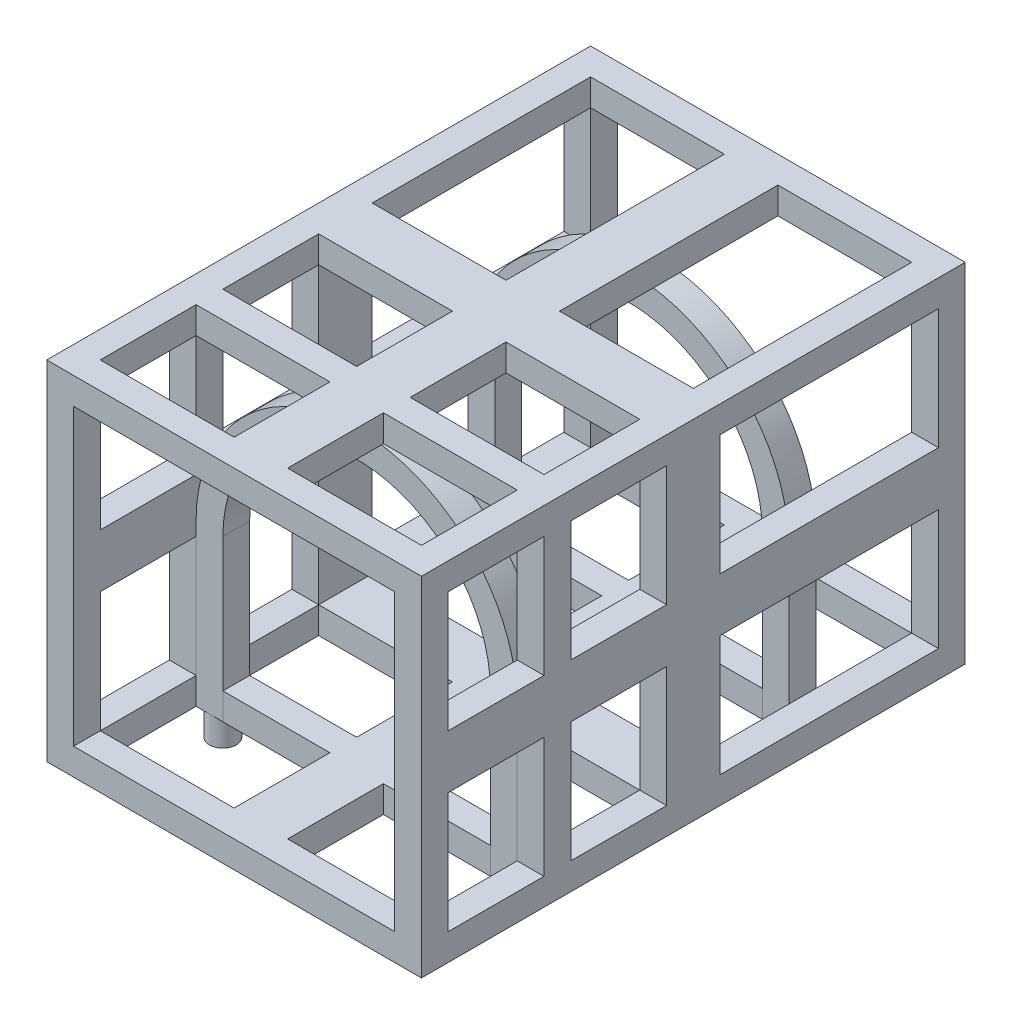
SolidWorks part; units mm, degrees
material "POLYURETHANE (11671)"
ref_plane "Front Plane" through (0, 0, 0) normal (0, 0, 1) x (1, 0, 0)
ref_plane "Top Plane" through (0, 0, 0) normal (0, 1, 0) x (1, 0, 0)
ref_plane "Right Plane" through (0, 0, 0) normal (1, 0, 0) x (0, 0, -1)
sketch "Chassis Frame Sketch" plane through (0, 0, 0) normal (0, 0, 1) x (1, 0, 0)
  line L0 (-60, 60) -> (60, 60)
  line L1 (-50, 50) -> (50, 50)
  line L2 (-50, 50) -> (-50, -50)
  line L3 (-60, -50) -> (60, -50)
  line L4 (50, 50) -> (50, -50)
  line L5 (60, 60) -> (60, -50)
  line L6 (-70, -60) -> (70, -60)
  line L7 (-60, 60) -> (-60, -50)
  line L8 (-70, 70) -> (70, 70)
  line L9 (70, 70) -> (70, -60)
  line L11 (-70, 70) -> (-70, -60)
  line L12 (-50, -50) -> (50, -50) construction
  line L13 (-60, -60) -> (60, -60) construction
  line L14 (-70, 70) -> (-70, -70) construction
  line L15 (-70, -70) -> (70, -70) construction
  line L16 (70, 70) -> (70, -70) construction
  line L17 (60, 60) -> (60, -60) construction
  line L18 (-60, 60) -> (-60, -60) construction
  circle A0 centre (0, 0) radius 50
  point P7 (0, 50)
  point P10 (-50, 0)
  dimension "D1" = 100
  dimension "D2" = 10
  dimension "D3" = 10
extrude "Chassis Frame" add sketch "Chassis Frame Sketch" along normal mid plane 203.2 separate body contours L8 L11 L9 L7 L0 L5 L6 region at (-68.0895, 5, 0)
ref_plane "Quarter Plane 1" through (0, 0, 50.8) normal (0, 0, 1) x (1, 0, 0)
sketch "U Bolt Sketch" plane through (0, 0, 50.8) normal (0, 0, 1) x (1, 0, 0)
  line L0 (-50, 0) -> (-50, -60)
  line L1 (50, 0) -> (50, -60)
  line L4 (-50, 50) -> (50, 50)
  line L5 (50, 50) -> (50, -50)
  line L7 (-50, -50) -> (-50, 50)
  line L11 (-50, -50) -> (-50, 0)
  line L12 (60, 60) -> (-60, 60)
  line L13 (60, -50) -> (60, 60)
  line L14 (-60, -50) -> (60, -50)
  line L15 (-60, 60) -> (-60, -50)
  line L16 (60, 60) -> (-60, 60)
  line L17 (60, -60) -> (60, 60)
  line L19 (-60, 60) -> (-60, -60)
  line L20 (70, -60) -> (70, 70)
  line L21 (-70, -60) -> (70, -60)
  line L22 (-70, 70) -> (-70, -60)
  line L23 (70, 70) -> (-70, 70)
  line L24 (70, -60) -> (70, 70)
  line L26 (-70, 70) -> (-70, -60)
  line L27 (70, 70) -> (-70, 70)
  line L28 (-50, -50) -> (50, -50)
  line L29 (-70, -60) -> (70, -60)
  arc A0 (60, 0) -> (-60, 0) centre (0, 0) ccw
  circle A1 centre (0, 0) radius 50
  circle A2 centre (0, 0) radius 50
  circle A3 centre (0, 0) radius 60 construction
  dimension "D1" = 0
  dimension "D2" = 0
  dimension "D3" = 0
  dimension "D4" = 0
  dimension "D5" = 10
extrude "U Bolt 1" add sketch "U Bolt Sketch" along normal mid plane 10 separate body contours A2 L1 L29 L17 A0 L19 L0 region at (-54.6989, -13.3319, 50.8) region at (-37.0703, 37.0703, 50.8) region at (-55, -55, 50.8) region at (0, 54.03, 50.8) region at (37.0703, 37.0703, 50.8) region at (54.6989, -13.3319, 50.8) region at (55, -55, 50.8)
mirror "U Bolt 2" about plane through (0, 0, 0) normal (0, 0, 1) of bodies 104
ref_plane "Plane4" through (0, -70, 0) normal (0, -1, 0) x (-1, 0, 0)
sketch "Sketch20" plane through (0, -70, 0) normal (0, -1, 0) x (-1, 0, 0)
  line L4 (60, -45.8) -> (50, -45.8)
  line L5 (50, -45.8) -> (50, -55.8)
  line L6 (50, -55.8) -> (60, -55.8)
  line L7 (60, -55.8) -> (60, -45.8)
  line L8 (60, -45.8) -> (50, -45.8)
  line L9 (50, -45.8) -> (50, -55.8)
  line L10 (50, -55.8) -> (60, -55.8)
  line L11 (60, -55.8) -> (60, -45.8)
  circle A0 centre (55, -50.8) radius 5
  circle A1 centre (-55, -50.8) radius 5
  dimension "D1" = 0
  dimension "D2" = 2
extrude "U Bolts Bolts 1" add sketch "Sketch20" against normal blind 10 separate body contours A0 | A1
mirror "U Bolts Bolts 2" about plane through (0, 0, 0) normal (0, 0, 1) of bodies 115 116
sketch "Sketch21" plane through (0, 70, 0) normal (0, 1, 0) x (1, 0, 0)
  line L0 (-60, 91.6) -> (60, 91.6)
  line L1 (-70, 101.6) -> (70, 101.6)
  line L2 (-70, 101.6) -> (-70, -101.6)
  line L3 (-70, -101.6) -> (70, -101.6)
  line L4 (70, 101.6) -> (70, -101.6)
  line L5 (60, 91.6) -> (60, -91.6)
  line L6 (-60, -91.6) -> (60, -91.6)
  line L7 (-60, 91.6) -> (-60, -91.6)
  line L8 (0, 0) -> (0, -91.6)
  line L9 (0, 0) -> (0, 91.6)
  line L10 (10, 0) -> (10, -91.6)
  line L11 (10, 0) -> (10, 91.6)
  line L12 (-10, 0) -> (-10, -91.6)
  line L13 (-10, 0) -> (-10, 91.6)
  line L14 (-60, 0) -> (60, 0)
  line L15 (-60, -10) -> (60, -10)
  line L16 (-60, 10) -> (60, 10)
  dimension "D1" = 10
  dimension "D2" = 10
  dimension "D3" = 10
  dimension "D4" = 10
  dimension "D5" = 10
extrude "Cut-Extrude2" cut sketch "Sketch21" against normal through all both and the other way through all contours L11 L16 L5 L0 | L15 L10 L6 L5 | L15 L7 L6 L12 | L7 L16 L13 L0 region at (-35, 70, -50.8) region at (35, 70, -50.8) region at (-35, 70, 50.8) region at (35, 70, 50.8)
sketch "Sketch22" plane through (70, 0, 0) normal (1, 0, 0) x (0, 0, -1)
  line L0 (-91.6, 60) -> (91.6, 60)
  line L1 (-101.6, 70) -> (101.6, 70)
  line L2 (-101.6, 70) -> (-101.6, -60)
  line L3 (-101.6, -60) -> (101.6, -60)
  line L4 (101.6, 70) -> (101.6, -60)
  line L5 (91.6, 60) -> (91.6, -50)
  line L6 (-91.6, -50) -> (91.6, -50)
  line L7 (-91.6, 60) -> (-91.6, -50)
  line L8 (-91.6, 5) -> (91.6, 5)
  line L9 (0, 60) -> (0, -50)
  line L10 (-10, 60) -> (-10, -50)
  line L11 (10, 60) -> (10, -50)
  line L12 (-91.6, -5) -> (91.6, -5)
  line L13 (-91.6, 15) -> (91.6, 15)
  dimension "D1" = 10
  dimension "D2" = 10
  dimension "D3" = 10
  dimension "D4" = 10
  dimension "D5" = 10
extrude "Cut-Extrude3" cut sketch "Sketch22" against normal through all both and the other way through all contours L7 L13 L10 L0 | L12 L7 L6 L10 | L12 L11 L6 L5 | L11 L13 L5 L0 region at (70, 37.5, 50.8) region at (70, 37.5, -50.8) region at (70, -27.5, 50.8) region at (70, -27.5, -50.8)
sketch "Sketch23" plane through (0, -60, 0) normal (0, 1, 0) x (1, 0, 0)
  line L0 (-55, -55.8) -> (-45.8155, -55.8)
  line L1 (-45.8155, -55.8) -> (60, -55.8)
  line L2 (60, -10) -> (60, -91.6) construction
  line L3 (60, -55.8) -> (60, -45.8)
  line L4 (60, -45.8) -> (-60, -45.8)
  line L5 (-60, -10) -> (-60, -91.6) construction
  line L6 (-60, -45.8) -> (-60, -55.8)
  line L7 (-60, -55.8) -> (-55, -55.8)
  line L8 (-10, -45.8) -> (-10, -55.8)
  line L9 (-10, -10) -> (-10, -91.6) construction
  line L10 (10, -45.8) -> (10, -55.8)
  line L11 (10, -10) -> (10, -91.6) construction
  circle A0 centre (-55, -50.8) radius 5 construction
  circle M7 centre (-55, -50.8) radius 5
extrude "Boss-Extrude10" add sketch "Sketch23" along normal blind 10 contours L6 L7 M7 | L4 L6 M7 | M7 | L8 L4 L0 L1 M7 | L4 L10 L1 L3 region at (-30.5517, -60, 50.8) region at (-55, -60, 50.8) region at (-58.8832, -60, 54.6832) region at (-58.8832, -60, 46.9168) region at (35, -60, 50.8)
sketch "Sketch24" plane through (0, -60, 0) normal (0, 1, 0) x (1, 0, 0)
  line L7 (10, 56.2) -> (10, 46.2)
  line L8 (-10, 56.2) -> (-10, 46.2)
  line L9 (-60, 55.8) -> (-60, 45.8)
  line L10 (-60, 45.8) -> (-55, 45.8)
  line L11 (-55, 45.8) -> (-45.8155, 45.8)
  line L12 (-45.8155, 45.8) -> (60, 45.8)
  line L13 (60, 55.8) -> (-60, 55.8)
  line L15 (60, 45.8) -> (60, 55.8)
  circle A0 centre (-55, 50.8) radius 5 construction
  circle A1 centre (-55, 50.8) radius 5
  circle M8 centre (-55, 50.8) radius 5
extrude "Boss-Extrude11" add sketch "Sketch24" along normal blind 10 contours L12 L15 L13 L11 M8 | M8 | L9 L10 M8 | L9 L10 L11 L12 L15 L13 region at (-58.8832, -60, -46.9168) region at (-55, -60, -50.8) region at (4.4579, -60, -50.8)
sketch "Sketch25" plane through (0, 0, 50.8) normal (0, 0, 1) x (1, 0, 0)
  line L0 (-70, 70) -> (70, 70) construction
  line L1 (-70, 70) -> (70, 70)
  line L2 (70, 70) -> (70, -60) construction
  line L3 (-70, -60) -> (70, -60) construction
  line L4 (-60, 60) -> (-60, -50)
  line L5 (60, 60) -> (-60, 60)
  line L6 (60, -50) -> (60, 60)
  line L7 (-60, -50) -> (60, -50)
  line L8 (-60, 60) -> (-60, -50)
  line L9 (60, 60) -> (-60, 60)
  line L10 (60, -50) -> (60, 60)
  line L11 (-60, -50) -> (60, -50)
  line L12 (-70, 70) -> (-70, -60) construction
  line L13 (70, 70) -> (70, -60)
  line L14 (-70, -60) -> (70, -60)
  line L15 (-70, 70) -> (-70, -60)
  dimension "D1" = 0
extrude "Boss-Extrude12" add sketch "Sketch25" along normal mid plane 10 contours L1 L15 L14 L13 L11 L8 L9 L10 region at (0, 68.0895, 50.8)
ref_plane "Plane5" through (0, 0, -50.8) normal (0, 0, 1) x (1, 0, 0)
ref_plane "Plane6" through (-60, -60, 55.8) normal (1, 0, 0) x (0, 0, -1)
